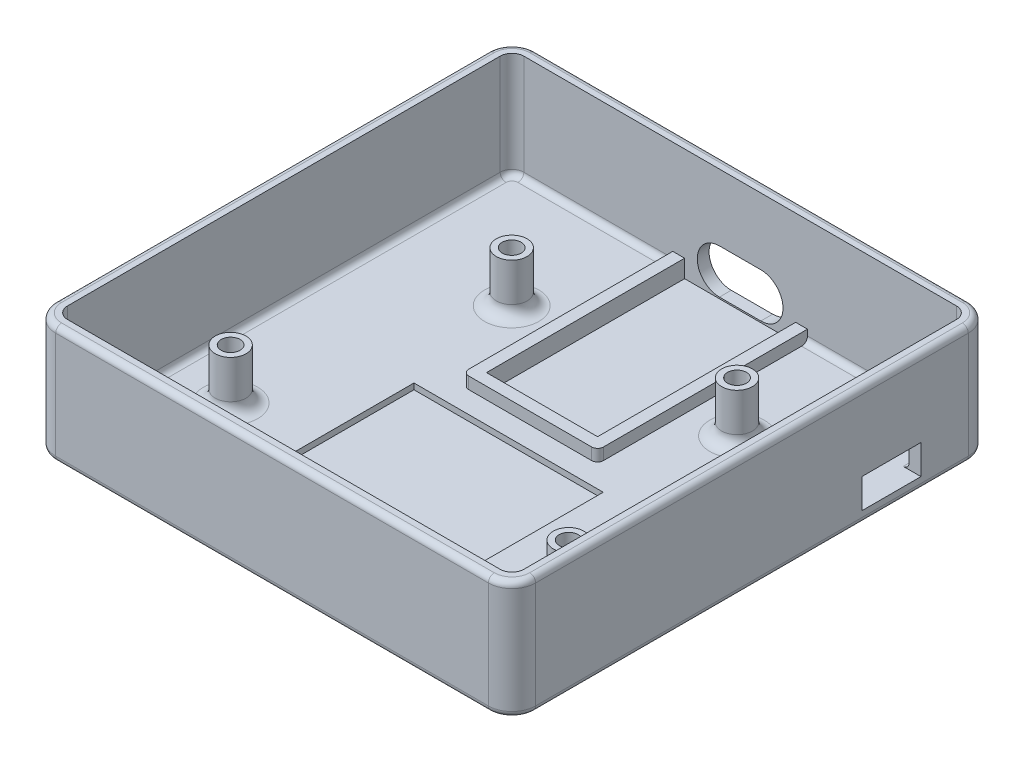
SolidWorks part; units mm, degrees
ref_plane "Front Plane" through (0, 0, 0) normal (0, 0, 1) x (1, 0, 0)
ref_plane "Top Plane" through (0, 0, 0) normal (0, 1, 0) x (1, 0, 0)
ref_plane "Right Plane" through (0, 0, 0) normal (1, 0, 0) x (0, 0, -1)
sketch "Sketch1" plane through (0, 0, 0) normal (0, 1, 0) x (1, 0, 0)
  line L1 (-38.575, -38.575) -> (38.575, -38.575)
  line L2 (-38.575, -38.575) -> (-38.575, 38.575)
  line L3 (-38.575, 38.575) -> (38.575, 38.575)
  line L4 (38.575, -38.575) -> (38.575, 38.575)
  line L5 (-38.575, -38.575) -> (38.575, 38.575) construction
  line L6 (-38.575, 38.575) -> (38.575, -38.575) construction
  point P0 (0, 0)
  dimension "D1" = 77.15
extrude "Boss-Extrude1" add sketch "Sketch1" along normal blind 2
sketch "Sketch2" plane through (0, 0, 0) normal (0, 1, 0) x (1, 0, 0)
  line L20 (38.575, -38.575) -> (38.575, 38.575) construction
  line L21 (38.575, 38.575) -> (-38.575, 38.575) construction
  line L22 (-38.575, 38.575) -> (-38.575, -38.575) construction
  line L23 (-38.575, -38.575) -> (38.575, -38.575) construction
  line L24 (40.575, -40.575) -> (40.575, 40.575)
  line L25 (40.575, 40.575) -> (-40.575, 40.575)
  line L26 (-40.575, 40.575) -> (-40.575, -40.575)
  line L27 (-40.575, -40.575) -> (40.575, -40.575)
  line L28 (40.575, -40.575) -> (40.575, 40.575)
  line L29 (40.575, 40.575) -> (-40.575, 40.575)
  line L30 (-40.575, 40.575) -> (-40.575, -40.575)
  line L31 (-40.575, -40.575) -> (40.575, -40.575)
  line L32 (38.575, -38.575) -> (38.575, 38.575)
  line L33 (38.575, 38.575) -> (-38.575, 38.575)
  line L34 (-38.575, 38.575) -> (-38.575, -38.575)
  line L35 (-38.575, -38.575) -> (38.575, -38.575)
  dimension "D1" = 2
extrude "Boss-Extrude2" add sketch "Sketch2" along normal blind 20
sketch "Sketch3" plane through (0, 2, 0) normal (0, 1, 0) x (1, 0, 0)
  line L0 (28.58, -19) -> (-28.58, -19) construction
  line L2 (19.05, 19) -> (-19.05, 19) construction
  circle A2 centre (-28.58, -19) radius 1.6
  circle A3 centre (28.58, -19) radius 1.6
  circle A4 centre (19.05, 19) radius 1.6
  circle A5 centre (-19.05, 19) radius 1.6
  circle A6 centre (-28.58, -19) radius 2.6
  circle A7 centre (-19.05, 19) radius 2.6
  circle A8 centre (28.58, -19) radius 2.6
  circle A9 centre (19.05, 19) radius 2.6
  point P0 (0, 0)
  point P2 (0, 19)
  point P17 (0, -19)
  dimension "D3" = 1
  dimension "D4" = 19
  dimension "D1" = 3.2
  dimension "D2" = 38.1
  dimension "D5" = 57.16
  dimension "D6" = 19
extrude "Boss-Extrude4" add sketch "Sketch3" along normal offset from surface (8.5 mm away) 9.5 up to face at (0, 20, 0)
sketch "Sketch4" plane through (0, 0, 0) normal (1, 0, 0) x (0, 0, -1)
  line L0 (0, 0) -> (0, 20) construction
  line L1 (-40.575, 20) -> (40.575, 20) construction
sketch "Sketch11" plane through (0, 2, 0) normal (0, 1, 0) x (1, 0, 0)
  line L0 (-15, -31.575) -> (-15, -1.575)
  line L6 (-16, -32.575) -> (16, -32.575)
  line L7 (-16, -32.575) -> (-16, -0.575)
  line L8 (-16, -0.575) -> (16, -0.575)
  line L9 (16, -32.575) -> (16, -0.575)
  line L10 (-16, -32.575) -> (16, -0.575) construction
  line L11 (-16, -0.575) -> (16, -32.575) construction
  line L12 (38.575, 38.575) -> (-38.575, 38.575) construction
  line L13 (-8.89, 38.575) -> (8.89, 38.575) construction
  line L14 (-8.89, 38.575) -> (-8.89, 5.575) construction
  line L15 (-8.89, 5.575) -> (8.89, 5.575) construction
  line L16 (8.89, 38.575) -> (8.89, 5.575) construction
  line L17 (-8.89, 38.575) -> (8.89, 5.575) construction
  line L18 (-8.89, 5.575) -> (8.89, 38.575) construction
  line L27 (-15, -1.575) -> (15, -1.575)
  line L28 (15, -31.575) -> (15, -1.575)
  line L29 (-15, -31.575) -> (15, -31.575)
  line L30 (0, -11) -> (0, 11) construction
  line L31 (4, 38.575) -> (5.5, 38.575)
  line L32 (4, 38.575) -> (4, 10.575)
  line L33 (4, 10.575) -> (5.5, 10.575)
  line L34 (5.5, 38.575) -> (5.5, 10.575)
  line L35 (-4, 10.575) -> (-5.5, 10.575)
  line L36 (-5.5, 38.575) -> (-5.5, 10.575)
  line L37 (-4, 38.575) -> (-5.5, 38.575)
  line L38 (-4, 38.575) -> (-4, 10.575)
  line L39 (-38.575, -38.575) -> (38.575, -38.575) construction
  point P1 (0, 22.075)
  point P6 (0, -16.575)
  dimension "D1" = 33
  dimension "D2" = 17.78
  dimension "D3" = 1
  dimension "D4" = 30
  dimension "D5" = 6
  dimension "D6" = 30
  dimension "D7" = 4
  dimension "D8" = 1.5
  dimension "D9" = 5
extrude "Boss-Extrude7" [suppressed] add sketch "Sketch11" along normal blind 1 contours L35 L36 L37 L38 | L32 L31 L34 L33
sketch "Sketch17" plane through (0, 2, 0) normal (0, 1, 0) x (1, 0, 0)
  line L16 (9.39, 11.075) -> (11.39, 11.075)
  line L17 (11.39, 11.075) -> (11.39, 3.075)
  line L18 (11.39, 3.075) -> (-11.39, 3.075)
  line L19 (-9.39, 5.075) -> (-9.39, 38.575)
  line L20 (9.39, 5.075) -> (-9.39, 5.075)
  line L21 (9.39, 38.575) -> (9.39, 5.075)
  line L22 (-9.39, 5.075) -> (-9.39, 11.075)
  line L23 (9.39, 5.075) -> (-9.39, 5.075)
  line L24 (9.39, 11.075) -> (9.39, 5.075)
  line L25 (-11.39, 3.075) -> (-11.39, 11.075)
  line L26 (-11.39, 11.075) -> (-9.39, 11.075)
  dimension "D1" = 0.5
  dimension "D2" = 2
  dimension "D3" = 2
  dimension "D4" = 8
extrude "Boss-Extrude8" [suppressed] add sketch "Sketch17" along normal blind 2
sketch "Sketch15" plane through (0, 2, 0) normal (0, 1, 0) x (1, 0, 0)
  line L0 (-16, -0.575) -> (-16, -8.575)
  line L1 (-16, -32.575) -> (-16, -0.575) construction
  line L2 (-16, -8.575) -> (-18, -8.575)
  line L3 (-18, -8.575) -> (-18, 1.425)
  line L4 (-18, 1.425) -> (-11, 1.425)
  line L5 (-11, 1.425) -> (-11, -0.575)
  line L6 (-16, -0.575) -> (16, -0.575) construction
  line L7 (-11, -0.575) -> (-16, -0.575)
  line L8 (-18, -24.575) -> (-16, -24.575)
  line L9 (-16, -24.575) -> (-16, -32.575)
  line L10 (-16, -32.575) -> (-11, -32.575)
  line L11 (-16, -32.575) -> (16, -32.575) construction
  line L12 (-11, -32.575) -> (-11, -34.575)
  line L13 (-11, -34.575) -> (-18, -34.575)
  line L14 (-18, -24.575) -> (-18, -34.575)
  line L15 (0, -11) -> (0, 11) construction
  line L16 (18, -24.575) -> (16, -24.575)
  line L17 (16, -24.575) -> (16, -32.575)
  line L18 (16, -32.575) -> (11, -32.575)
  line L19 (11, -32.575) -> (11, -34.575)
  line L20 (11, -34.575) -> (18, -34.575)
  line L21 (18, -24.575) -> (18, -34.575)
  line L22 (11, 1.425) -> (11, -0.575)
  line L23 (18, 1.425) -> (11, 1.425)
  line L24 (18, -8.575) -> (18, 1.425)
  line L25 (16, -8.575) -> (18, -8.575)
  line L26 (16, -0.575) -> (16, -8.575)
  line L27 (11, -0.575) -> (16, -0.575)
  dimension "D1" = 7
  dimension "D2" = 10
  dimension "D4" = 2
extrude "Boss-Extrude6" [suppressed] add sketch "Sketch15" along normal blind 1.5 contours L7 L0 L2 L3 L4 L5 | L22 L27 L26 L25 L24 L23 | L14 L13 L12 L10 L9 L8 | L16 L17 L18 L19 L20 L21
sketch "Sketch18" plane through (0, 2, 0) normal (0, 1, 0) x (1, 0, 0)
  line L0 (16, -32.575) -> (16, -0.575) construction
  line L1 (-16, -0.575) -> (16, -0.575) construction
  line L2 (-16, -32.575) -> (-16, -0.575) construction
  line L3 (-16, -32.575) -> (16, -32.575) construction
  line L4 (16, -32.575) -> (16, -0.575)
  line L5 (-16, -0.575) -> (16, -0.575)
  line L6 (-16, -32.575) -> (-16, -0.575)
  line L7 (-16, -32.575) -> (16, -32.575)
  line L21 (-8.89, 38.575) -> (8.89, 38.575) construction
  line L22 (-9.39, 38.575) -> (9.39, 38.575)
  line L24 (-9.39, 5.075) -> (-9.39, 38.575)
  line L25 (9.39, 5.075) -> (-9.39, 5.075)
  line L26 (9.39, 38.575) -> (9.39, 5.075)
  line L27 (-9.39, 5.075) -> (-9.39, 38.575)
  line L28 (9.39, 5.075) -> (-9.39, 5.075)
  line L29 (9.39, 38.575) -> (9.39, 5.075)
  dimension "D1" = 0.5
extrude "Cut-Extrude4" cut sketch "Sketch18" against normal offset from surface (1 mm away) 1 up to face at (0, 0, 0)
sketch "Sketch19" plane through (0, 2, 0) normal (0, 1, 0) x (1, 0, 0)
  line L0 (-9.39, 38.575) -> (-9.39, 5.075) construction
  line L1 (-9.39, 5.075) -> (9.39, 5.075) construction
  line L2 (9.39, 5.075) -> (9.39, 38.575) construction
  line L3 (-9.39, 38.575) -> (-9.39, 5.075)
  line L4 (-9.39, 5.075) -> (9.39, 5.075)
  line L5 (9.39, 5.075) -> (9.39, 38.575)
  line L6 (-11.39, 38.575) -> (-11.39, 3.075)
  line L7 (-11.39, 3.075) -> (11.39, 3.075)
  line L8 (11.39, 3.075) -> (11.39, 38.575)
  line L9 (11.39, 38.575) -> (9.39, 38.575)
  line L10 (-9.39, 38.575) -> (-11.39, 38.575)
  dimension "D1" = 2
extrude "Boss-Extrude9" add sketch "Sketch19" along normal blind 2
sketch "Sketch7" plane through (0, 0, 0) normal (0, -1, 0) x (1, 0, 0)
  line L0 (40.575, -40.575) -> (-40.575, -40.575) construction
  line L1 (-40.575, -40.575) -> (-40.575, 40.575) construction
  line L2 (0, 0) -> (-24.575, -24.575) construction
  circle A0 centre (-24.575, -24.575) radius 6.35
  circle A1 centre (-24.575, 24.575) radius 6.35
  circle A2 centre (24.575, 24.575) radius 6.35
  circle A3 centre (24.575, -24.575) radius 6.35
  dimension "D1" = 12.7
  dimension "D4" = 4
extrude "Cut-Extrude1" cut sketch "Sketch7" against normal offset from surface (1 mm away) 1 up to face at (0, 2, 16.575)
sketch "Sketch10" plane through (0, 0, -38.575) normal (0, 0, -1) x (-1, 0, 0)
  line L0 (-3.5, 5) -> (3.5, 5) construction
  line L1 (-3.5, 8.75) -> (3.5, 8.75)
  line L2 (-3.5, 1.25) -> (3.5, 1.25)
  line L3 (-38.575, 2) -> (-11.39, 2) construction
  line L4 (-38.575, 2) -> (-11.39, 2) construction
  line L5 (-9.39, 1) -> (9.39, 1) construction
  arc A1 (-3.5, 8.75) -> (-3.5, 1.25) centre (-3.5, 5) ccw
  arc A2 (3.5, 1.25) -> (3.5, 8.75) centre (3.5, 5) ccw
  point P2 (0, 5)
  dimension "D1" = 7
  dimension "D2" = 7.5
  dimension "D3" = 4
extrude "Cut-Extrude2" cut sketch "Sketch10" along normal up to surface (2 mm away) up to face at (0, 10, -40.575)
sketch "Sketch16" plane through (38.575, 0, 0) normal (-1, 0, 0) x (0, 0, 1)
  line L0 (38.575, 2) -> (-38.575, 2) construction
  line L1 (-28.575, 2) -> (-18.575, 2)
  line L2 (-28.575, 2) -> (-28.575, 7)
  line L3 (-28.575, 7) -> (-18.575, 7)
  line L4 (-18.575, 2) -> (-18.575, 7)
  dimension "D1" = 10
  dimension "D2" = 5
  dimension "D3" = 10
extrude "Cut-Extrude3" cut sketch "Sketch16" against normal up to surface (2 mm away) up to face at (40.575, 10, 0)
fillet "Fillet1" radius 2 4 edges at (28.58, 2, 16.4) (19.05, 2, -21.6) (-28.58, 2, 16.4) (-19.05, 2, -21.6)
fillet "Fillet2" [suppressed] radius 1
chamfer "Chamfer1" [suppressed] distance 2.5 angle 45
fillet "Fillet3" [suppressed] radius 2 tangent propagation no
fillet "Fillet6" radius 4 4 edges at (40.575, 10, -40.575) (-40.575, 10, -40.575) (-40.575, 10, 40.575) (40.575, 10, 40.575)
fillet "Fillet7" radius 2 4 edges at (38.575, 11, -38.575) (-38.575, 11, -38.575) (-38.575, 11, 38.575) (38.575, 11, 38.575)
fillet "Fillet5" radius 1 16 edges at (0, 20, 40.575) (-40.575, 20, 0) (0, 20, -40.575) (0, 0, 40.575) (-40.575, 0, 0) (0, 0, -40.575) (40.575, 20, 0) (40.575, 0, 0) (39.4034, 0, 39.4034) (-39.4034, 0, 39.4034) (-39.4034, 0, -39.4034) (39.4034, 0, -39.4034) (39.4034, 20, 39.4034) (-39.4034, 20, 39.4034) (-39.4034, 20, -39.4034) (39.4034, 20, -39.4034)
fillet "Fillet9" radius 1 10 edges at (23.9825, 2, -38.575) (37.9892, 2, -37.9892) (38.575, 2, 9) (37.9892, 2, 37.9892) (0, 2, 38.575) (-37.9892, 2, 37.9892) (-38.575, 2, 0) (-37.9892, 2, -37.9892) (38.575, 2, -32.575) (-23.9825, 2, -38.575)
fillet "Fillet10" radius 1 2 edges at (-11.39, 3, -3.075) (11.39, 3, -3.075)
